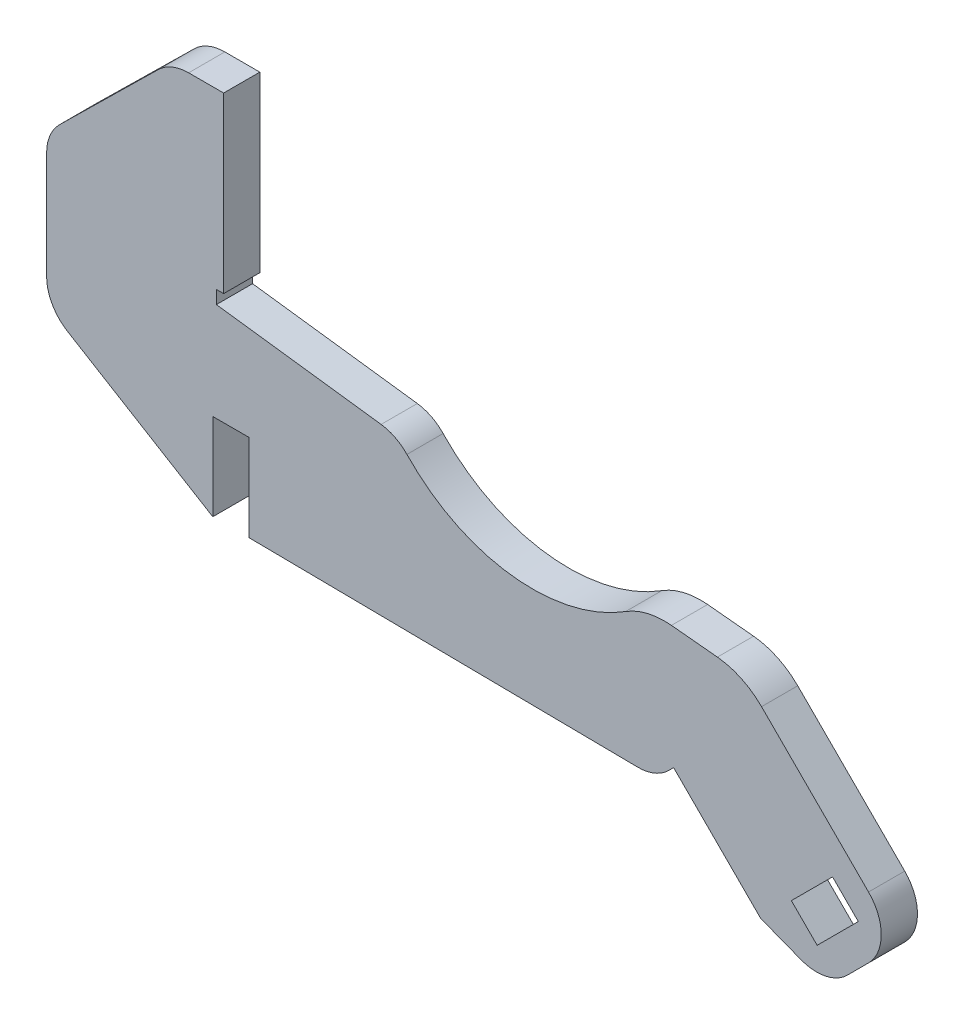
SolidWorks part; units mm, degrees
material "PBT General Purpose"
ref_plane "Front Plane" through (0, 0, 0) normal (0, 0, 1) x (1, 0, 0)
ref_plane "Top Plane" through (0, 0, 0) normal (0, 1, 0) x (1, 0, 0)
ref_plane "Right Plane" through (0, 0, 0) normal (1, 0, 0) x (0, 0, -1)
sketch "frame_outline" plane through (0, 0, 0) normal (0, 0, 1) x (1, 0, 0)
  line L0 (0, 0) -> (0, -0.4) construction
  line L1 (0, 0) -> (0.3, 0) construction
  line L2 (0, -0.4) -> (-0.05, -0.4) construction
  line L3 (0, 0) -> (4.9667, -4.9667) construction
  line L63 (-0.05, -0.4) -> (-0.05, -1.6)
  line L64 (-0.05, -0.4) -> (-0.4144, -0.4)
  line L65 (-0.4144, -0.4) -> (-1.2727, -1.2438)
  line L66 (-1.2727, -1.2438) -> (-1.2727, -2.2778)
  line L67 (-1.2727, -2.2778) -> (-0.125, -2.9724)
  line L68 (-0.125, -2.9724) -> (-0.125, -2.3724)
  line L69 (-0.125, -2.3724) -> (0.125, -2.3724)
  line L70 (0.125, -2.3724) -> (0.125, -2.9724)
  line L71 (0.125, -2.9724) -> (2.9356, -3.0041)
  line L72 (2.9356, -3.0041) -> (3.0582, -2.8815)
  line L73 (3.0582, -2.8815) -> (3.6593, -3.4825)
  line L74 (3.6593, -3.4825) -> (4.1203, -3.6607)
  line L75 (4.1203, -3.6607) -> (4.6167, -3.1643)
  line L76 (4.6167, -3.1643) -> (3.5388, -2.0864)
  line L77 (3.5388, -2.0864) -> (2.8549, -2.0196)
  line L78 (-0.1, -1.6906) -> (-0.1, -1.6)
  line L79 (-0.1, -1.6) -> (-0.05, -1.6)
  line L80 (3.8714, -3.2704) -> (4.0496, -3.4486)
  line L81 (3.8714, -3.2704) -> (4.1557, -2.9861)
  line L82 (4.0496, -3.4486) -> (4.3339, -3.1643)
  line L83 (4.1557, -2.9861) -> (4.3339, -3.1643)
  line L84 (0, -0.4) -> (0, -4.6335) construction
  line L85 (3.6593, -3.4825) -> (3.8714, -3.2704) construction
  line L86 (1.1495, -1.8531) -> (-0.1, -1.6906)
  arc A0 (1.1495, -1.8531) -> (2.8549, -2.0196) centre (2.0839, -1.1001) ccw
  point P25 (0, -2.3724)
  dimension "D2" = 0.3
  dimension "D3" = 0.4
  dimension "D8" = 1.2
  dimension "D4" = 45
  dimension "D1" = 0.05
  dimension "D5" = 0.125
  dimension "D6" = 0.25
  dimension "D7" = 0.05
  dimension "D9" = 0.6
  dimension "D10" = 0.85
  dimension "D11" = 0.252
  dimension "D12" = 0.402
  dimension "D13" = 0.3
  dimension "D14" = 0.2
  dimension "D15" = 0.2
  dimension "D16" = 0.1
  dimension "D17" = 4.2
extrude "Boss-Extrude1" add sketch "frame_outline" along normal mid plane 0.25
fillet "Fillet1" radius 0.3 7 edges at (4.6167, -3.1643, 0) (4.1203, -3.6607, 0) (1.1495, -1.8531, 0) (-0.4144, -0.4, 0) (-1.2727, -1.2438, 0) (-1.2727, -2.2778, 0) (2.9356, -3.0041, 0)
fillet "Fillet2" radius 0.5 2 edges at (3.5388, -2.0864, 0) (2.8549, -2.0196, 0)
equation "\"t\"= 0.25'thickness of the sheets"
equation "\"t_cf\"= 0.115'thickness of single carbon fiber layer"
equation "\"t_kapton\"= 0.025'thickness of single Kapton flex layer"
equation "\"t_fr4\"= 0.1'thickness of FR4 with copper layer"
equation "\"joint_flex\"= 0.1'Width of flextures gap"
equation "\"joint_flex_eff\"= 0.02'Width of flecture after castelation"
equation "\"joint_fold\"= 0.2'Width of folding joints for 90deg fold"
equation "\"gap_tolerance\"= 0.002'Width to have interfecence fit between carbon fiber inserts"
equation "\"assemble_angle\"= 90'Angle of assembly parts"
equation "\"D1@Boss-Extrude1\"=\"t\""
equation "\"link_lift\"= 0.5'Actuation linkage amplification for the lift motion"
equation "\"link_swing\"= 0.45'Actuation linkage amplification for the swing motion"
equation "\"D1@frame_outline\"=\"joint_flex\"/2"
equation "\"D5@frame_outline\"=\"t\"/2"
equation "\"D6@frame_outline\"=\"t\""
equation "\"D11@frame_outline\"=\"t\"+\"gap_tolerance\""
equation "\"D12@frame_outline\"=0.4+\"gap_tolerance\""
equation "\"D10@frame_outline\"=0.80mm+0.05"
